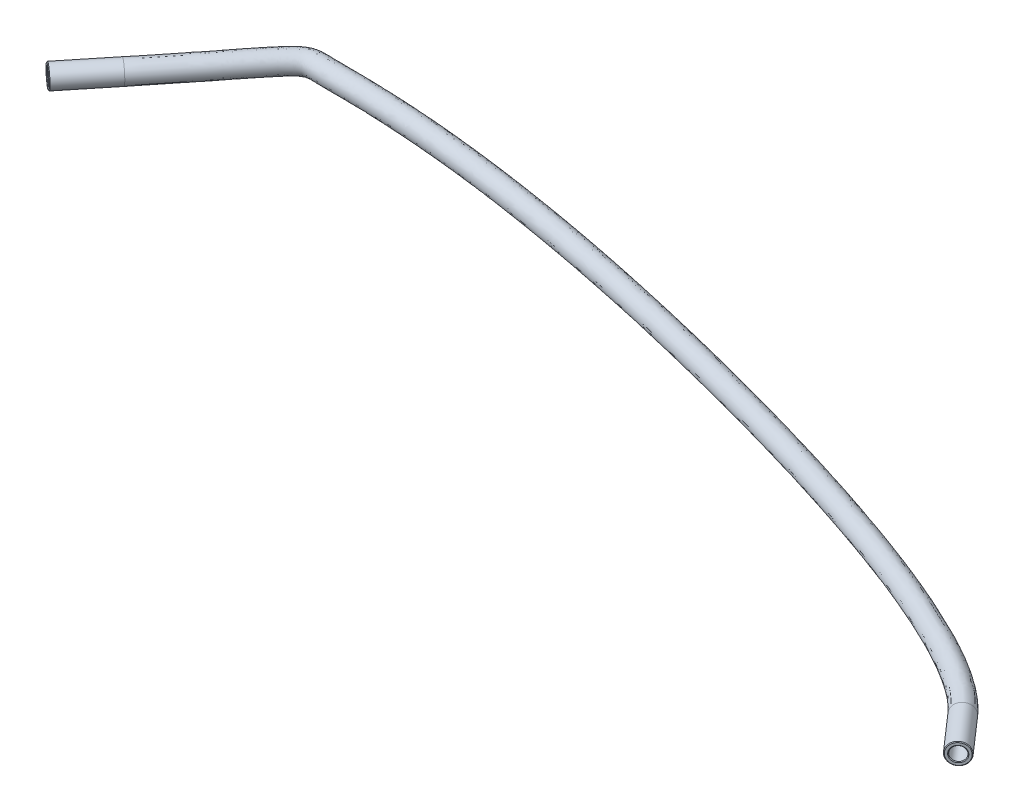
SolidWorks part; units mm, degrees
ref_plane "Front Plane" through (0, 0, 0) normal (0, 0, 1) x (1, 0, 0)
ref_plane "Top Plane" through (0, 0, 0) normal (0, 1, 0) x (1, 0, 0)
ref_plane "Right Plane" through (0, 0, 0) normal (1, 0, 0) x (0, 0, -1)
sketch3d "3DSketch1"
  line L0 (-99.7526, -99.5875, -21.9249) -> (-106.1664, -99.5875, -13.9938)
  line L1 (91.1644, -99.6875, 10.8405) -> (85.1041, -99.6875, 3.9186)
  spline S0 degree 3 poles (85.1041, -99.6875, 3.9186) (73.305, -99.6875, -9.5581) (-38.0017, -99.6522, -42.8291) (-88.4222, -99.6022, -40.2685) (-83.5026, -99.5875, -42.019) (-99.7526, -99.5875, -21.9249) knots 0 0 0 0 0.304238 0.705959 1 1 1 1
sketch "Sketch1" plane through (40.2541, 0, 45.9771) normal (-0.6587, 0, -0.7524) x (-0.7524, 0, 0.6587)
  circle A0 centre (-61.4494, -99.6875) radius 2
  circle A1 centre (-61.4494, -99.6875) radius 1.3
  circle A4 centre (-61.4494, -99.6875) radius 3.5524 construction
  dimension "D1" = 2.6
  dimension "D2" = 4
sweep "Sweep1" add profiles "Sketch1" path "3DSketch1"
chamfer "Chamfer1" distance 0.127 angle 45 4 edges at (-104.6113, -99.5912, -12.7362) (-105.1556, -99.5899, -13.1764) (89.6597, -99.6875, 12.158) (90.1863, -99.6875, 11.6968)
